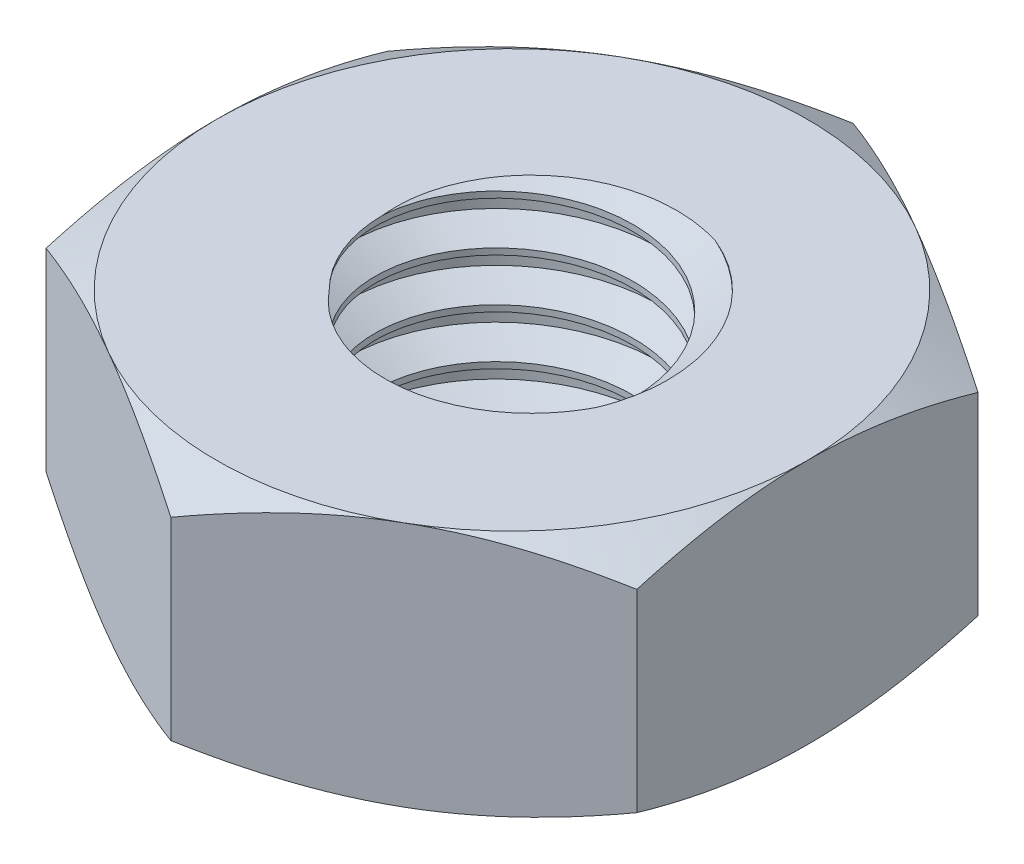
SolidWorks part; units mm, degrees
ref_plane "Front Plane" through (0, 0, 0) normal (0, 0, 1) x (1, 0, 0)
ref_plane "Top Plane" through (0, 0, 0) normal (0, 1, 0) x (1, 0, 0)
ref_plane "Right Plane" through (0, 0, 0) normal (1, 0, 0) x (0, 0, -1)
sketch "Sketch1" plane through (0, 0, 0) normal (0, 1, 0) x (1, 0, 0)
  line L1 (0, 13.8564) -> (-12, 6.9282)
  line L2 (-12, 6.9282) -> (-12, -6.9282)
  line L3 (-12, -6.9282) -> (0, -13.8564)
  line L4 (0, -13.8564) -> (12, -6.9282)
  line L5 (12, -6.9282) -> (12, 6.9282)
  line L6 (12, 6.9282) -> (0, 13.8564)
  circle A0 centre (0, 0) radius 12 construction
  point P1 (0, 0)
  dimension "D1" = 24
extrude "Boss-Extrude1" add sketch "Sketch1" along normal mid plane 10
hole_wizard "M12x1.5 Tapped Hole1" positions "Sketch3" profile "Sketch4" tap size "M12x1.5" standard "ANSI Metric" end condition through all
sketch "Sketch3" plane through (0, -5, 0) normal (0, -1, 0) x (-1, 0, 0)
  point P0 (0, 0)
sketch "Sketch4" plane through (0, -5, 0) normal (1, 0, 0) x (0, 0, -1)
  line L0 (0, 0) -> (0, 10)
  line L1 (0, 10) -> (5.25, 10)
  line L2 (5.25, 10) -> (5.25, 0)
  line L5 (5.25, 0) -> (0, 0)
  line L11 (0, -6.35) -> (0, 107.95) construction
  dimension "Thru Tap Drill Dia." = 10.5
  dimension "Thru Tap Drill Depth" = 10
cosmetic thread "Hole Thread1" parameters "D2"=12
thread "Thread1" pitch 2 method cut trim with start face yes trim with end face yes profile "Thread Profile1" start angle 0, offset 5, length 40, pitch 2, diameter 10.5
ref_plane "Plane1" through (5.25, -10, 0) normal (0, 0, -1) x (-1, 0, 0)
sketch "Thread Profile1" plane through (5.25, -10, 0) normal (0, 0, -1) x (-1, 0, 0)
  line L0 (0, 0) -> (0, 2) construction
  line L11 (0, 0) -> (0, 1.75)
  line L12 (0, 1.75) -> (-1.0825, 1.125)
  line L13 (-1.0825, 1.125) -> (-1.0825, 0.625)
  line L15 (-1.0825, 0.625) -> (0, 0)
  line L17 (-1.0825, 0.875) -> (0, 0.875) construction
  point P2 (0, 0)
  dimension "Pitch" = 2
  dimension "Profile_Angle" = 60
  dimension "Profile_Land" = 0.5
  dimension "Profile_Height" = 1.0825
sketch "Sketch7" plane through (0, -5, 0) normal (0, -1, 0) x (1, 0, 0)
  line L0 (-12, -6.9282) -> (-12, 6.9282) construction
  circle A0 centre (0, 0) radius 12
extrude "Cut-Extrude1" cut sketch "Sketch7" against normal through all draft 60 flip side to cut
mirror "Mirror1" about plane through (0, 0, 0) normal (0, 1, 0) of "Cut-Extrude1"
